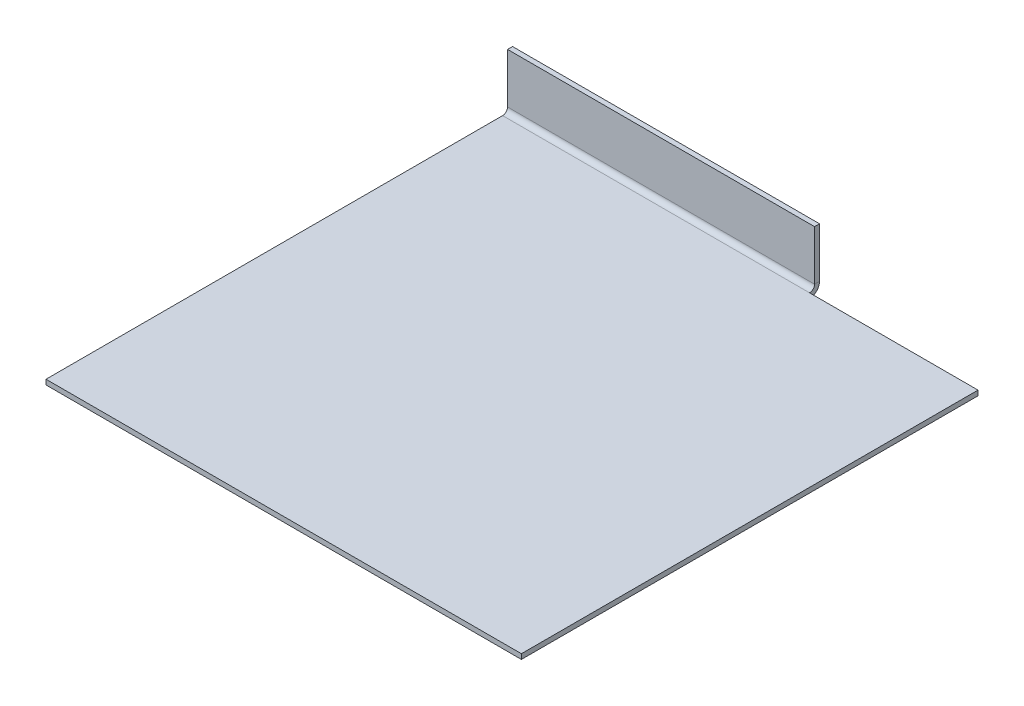
SolidWorks part; units mm, degrees
note: The reader was unsure of these and kept them because the rebuilt part matched: flange length of "Edge-Flange1".
material "6061-T6 (SS)"
ref_plane "X-Y Datum" through (0, 0, 0) normal (0, 0, 1) x (1, 0, 0)
ref_plane "X-Z Datum" through (0, 0, 0) normal (0, 1, 0) x (1, 0, 0)
ref_plane "Y-Z Datum" through (0, 0, 0) normal (1, 0, 0) x (0, 0, -1)
sketch "Sketch1" plane through (0, 0, 0) normal (0, 1, 0) x (1, 0, 0)
  line L0 (0, 290.83) -> (-101.6, 290.83)
  line L1 (0, 0) -> (201.2086, 0)
  line L3 (0, 290.83) -> (201.2086, 290.83)
  line L4 (201.2086, 0) -> (201.2086, 290.83)
  line L5 (-101.6, 290.83) -> (-101.6, 0)
  line L6 (-101.6, 0) -> (0, 0)
base flange "Base-Flange1" sketch "Sketch1" thickness 3.175 reverse thickness direction no parameters "D1"=3.175
edge flange "Edge-Flange1" sketch "Sketch8" flange angle 90 flange length 38.1 flange position bend outside bend radius 3.175 thickness 3.175 relief rectangular parameters "D6"=10
sketch "Sketch8" plane through (0, 0, -290.83) normal (0, 0, -1) x (-1, 0, 0)
  line L0 (-201.2086, 0) -> (101.6, 0) construction
  line L3 (-93.9215, 34.925) -> (101.6, 34.925)
  line L4 (101.6, 34.925) -> (101.6, 0)
  line L9 (-93.9215, 34.925) -> (-93.9215, 0)
  line L11 (-93.9215, 0) -> (101.6, 0)
bend "EdgeBend1" bend radius 3.175 bend angle 90 parameters "D5"=1
sketch "Bend-Lines1" [suppressed] plane through (0, 0, 0) normal (0, 1, 0) x (1, 0, 0)
sketch "Bounding-Box1" [suppressed] plane through (0, 0, 0) normal (0, 1, 0) x (1, 0, 0)
sheet metal parameters "Sheet-Metal1" thickness 3.175 parameters "D1"=3.175
flat pattern "Flat-Pattern1" [suppressed]
sketch "Bend-Lines2" plane through (0, 0, 0) normal (0, 1, 0) x (1, 0, 0)
sketch3d "Bounding-Box2" [suppressed]
  line L0 (0, 0, 0) -> (0, 290.83, 0) construction
  line L1 (-201.2086, 0, 0) -> (-201.2086, 290.83, 0) construction
  line L2 (0, 0, 0) -> (-201.2086, 0, 0) construction
  line L3 (0, 290.83, 0) -> (-201.2086, 290.83, 0) construction
sheet metal parameters "Sheet-Metal2" thickness 3.175 parameters "D1"=3.175
flat pattern "Flat-Pattern1"
sketch "Bend-Lines2" plane through (0, 0, 0) normal (0, 1, 0) x (1, 0, 0)
  line L0 (93.9215, 294.5705) -> (-101.6, 294.5705) construction
  line L1 (93.9215, 294.5705) -> (-101.6, 294.5705) construction
sketch3d "Bounding-Box2" [suppressed]
  line L0 (-101.6, 330.0609, 0) -> (-101.6, 0, 0) construction
  line L1 (201.2086, 330.0609, 0) -> (201.2086, 0, 0) construction
  line L2 (-101.6, 330.0609, 0) -> (201.2086, 330.0609, 0) construction
  line L3 (-101.6, 0, 0) -> (201.2086, 0, 0) construction
bend of the flat pattern "Flatten-<EdgeBend1>1"
